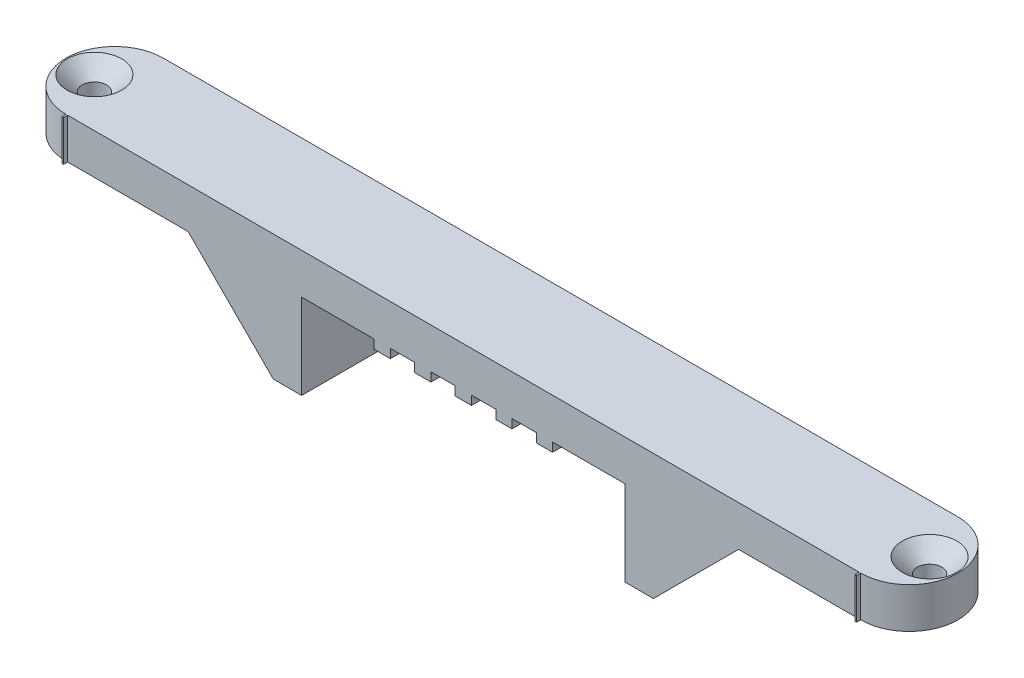
SolidWorks part; units mm, degrees
ref_plane "Front Plane" through (0, 0, 0) normal (0, 0, 1) x (1, 0, 0)
ref_plane "Top Plane" through (0, 0, 0) normal (0, 1, 0) x (1, 0, 0)
ref_plane "Right Plane" through (0, 0, 0) normal (1, 0, 0) x (0, 0, -1)
sketch "Sketch1" plane through (0, 0, 0) normal (0, 1, 0) x (1, 0, 0)
  line L0 (-49, 0) -> (49, 0) construction
  line L1 (-49, 6) -> (49, 6)
  line L2 (-49, -6) -> (49, -6)
  arc A0 (-49, 6) -> (-49, -6) centre (-49, 0) ccw
  arc A1 (49, -6) -> (49, 6) centre (49, 0) ccw
  circle A2 centre (-51.5, 0) radius 1.5
  circle A3 centre (51.5, 0) radius 1.5
  point P2 (0, 0)
  point P12 (-55, 0)
  point P13 (55, 0)
  dimension "D3" = 3
  dimension "D4" = 3.5
  dimension "D1" = 110
  dimension "D2" = 12
  dimension "D5" = 3.5
extrude "Boss-Extrude1" add sketch "Sketch1" along normal blind 3 contours L2 A1 L1 A0 | A2 | A3
sketch "Sketch4" plane through (0, 0, 0) normal (0, -1, 0) x (1, 0, 0)
  line L0 (-19.94, 6) -> (-19.94, -6)
  line L1 (-49, 6) -> (49, 6) construction
  line L2 (-49, -6) -> (49, -6) construction
  line L3 (-19.94, -6) -> (-23.44, -6)
  line L4 (-23.44, -6) -> (-23.44, 6)
  line L5 (-23.44, 6) -> (-19.94, 6)
  line L6 (0, 6) -> (0, -6) construction
  line L7 (-19.94, 5.075) -> (-19.94, -14.3256) construction
  line L8 (23.44, -6) -> (23.44, 6)
  line L9 (19.94, -6) -> (23.44, -6)
  line L10 (19.94, 6) -> (19.94, -6)
  line L11 (23.44, 6) -> (19.94, 6)
  dimension "D1" = 0
  dimension "D2" = 3.5
extrude "Boss-Extrude3" add sketch "Sketch4" along normal blind 10.5
sketch "Sketch5" plane through (0, 0, 0) normal (0, -1, 0) x (1, 0, 0)
  line L1 (4, 6) -> (4, -6)
  line L2 (4, 6) -> (6, 6)
  line L6 (-19.94, -6) -> (19.94, -6) construction
  line L7 (-1, 6) -> (1, 6)
  line L8 (-1, 6) -> (-1, -6)
  line L9 (-1, -6) -> (1, -6)
  line L10 (1, 6) -> (1, -6)
  line L11 (-1, 6) -> (1, -6) construction
  line L12 (-1, -6) -> (1, 6) construction
  line L13 (6, 6) -> (6, -6)
  line L14 (4, -6) -> (6, -6)
  line L15 (9, 6) -> (9, -6)
  line L16 (9, 6) -> (11, 6)
  line L17 (11, 6) -> (11, -6)
  line L18 (9, -6) -> (11, -6)
  line L19 (-4, 6) -> (-4, -6)
  line L20 (-6, -6) -> (-4, -6)
  line L21 (-6, 6) -> (-6, -6)
  line L22 (-6, 6) -> (-4, 6)
  line L23 (-9, 6) -> (-9, -6)
  line L24 (-11, -6) -> (-9, -6)
  line L25 (-11, 6) -> (-11, -6)
  line L26 (-11, 6) -> (-9, 6)
  point P0 (0, 0)
  dimension "D1" = 2
  dimension "D2" = 3
  dimension "D3" = 3
extrude "Boss-Extrude4" add sketch "Sketch5" along normal blind 1.1
sketch "Sketch6" plane through (0, 0, 6) normal (0, 0, 1) x (1, 0, 0)
  line L0 (49, 0) -> (49, 3)
  line L1 (49, 3) -> (48.8, 3)
  line L2 (-49, 3) -> (49, 3) construction
  line L3 (48.8, 3) -> (48.8, 0)
  line L4 (23.44, 0) -> (49, 0) construction
  line L5 (48.8, 0) -> (49, 0)
  line L6 (0, 0) -> (0, 3) construction
  line L7 (-48.8, 0) -> (-49, 0)
  line L8 (-48.8, 3) -> (-48.8, 0)
  line L9 (-49, 3) -> (-48.8, 3)
  line L10 (-49, 0) -> (-49, 3)
  dimension "D1" = 0.2
extrude "Boss-Extrude5" add sketch "Sketch6" along normal blind 0.5 contours L0 L1 L3 L5 | L8 L7 L10 L9
chamfer "Chamfer1" distance 10.5 2 edges at (23.44, 0, 0) (-23.44, 0, 0)
hole_wizard "Ø3.0mm Dowel Hole1" positions "Sketch7" profile "Sketch9" hole size "Ø3.0" standard "ANSI Metric" end condition up to next
sketch "Sketch7" plane through (0, 3, 0) normal (0, 1, 0) x (1, 0, 0)
  point P0 (-51.5, 0)
  point P2 (51.5, 0)
sketch "Sketch9" plane through (-51.5, 3, 0) normal (1, 0, 0) x (0, 0, 1)
  line L0 (0, 0) -> (0, 13.5)
  line L1 (0, 13.5) -> (1.5, 13.5)
  line L2 (1.5, 13.5) -> (1.5, 0)
  line L5 (1.5, 0) -> (0, 0)
  line L11 (0, -6.35) -> (0, 107.95) construction
  dimension "Thru Hole Dia." = 3
  dimension "Thru Hole Depth" = 13.5
sketch "Sketch10" plane through (0, 3, 0) normal (0, 1, 0) x (1, 0, 0)
  line L8 (-49, -6) -> (-49, -6.5)
  line L9 (-49, -6.5) -> (-48.8, -6.5)
  line L10 (-48.8, -6.5) -> (-48.8, -6)
  line L11 (-48.8, -6) -> (48.8, -6)
  line L12 (48.8, -6) -> (48.8, -6.5)
  line L13 (48.8, -6.5) -> (49, -6.5)
  line L14 (49, -6.5) -> (49, -6)
  line L15 (49, 6) -> (-49, 6)
  line L16 (-49, -6) -> (-49, -6.5)
  line L17 (-49, -6.5) -> (-48.8, -6.5)
  line L18 (-48.8, -6.5) -> (-48.8, -6)
  line L19 (-48.8, -6) -> (48.8, -6)
  line L20 (48.8, -6) -> (48.8, -6.5)
  line L21 (48.8, -6.5) -> (49, -6.5)
  line L22 (49, -6.5) -> (49, -6)
  line L23 (49, 6) -> (-49, 6)
  circle A0 centre (-51.5, 0) radius 1.5 construction
  circle A1 centre (-51.5, 0) radius 1.5
  arc A2 (-49, 6) -> (-49, -6) centre (-49, 0) ccw
  arc A3 (49, -6) -> (49, 6) centre (49, 0) ccw
  arc A4 (-49, 6) -> (-49, -6) centre (-49, 0) ccw
  arc A5 (49, -6) -> (49, 6) centre (49, 0) ccw
  circle A6 centre (51.5, 0) radius 1.5 construction
  circle A7 centre (51.5, 0) radius 1.5
  dimension "D1" = 0
extrude "Boss-Extrude6" add sketch "Sketch10" along normal blind 2 contours A4 L16 L17 L18 L19 L20 L21 L22 A5 L23
hole_wizard "CSK for M3 SFHCS1" positions "Sketch11" profile "Sketch12" countersink size "M3" standard "ANSI Metric"
sketch "Sketch11" plane through (0, 5, 0) normal (0, 1, 0) x (1, 0, 0)
  point P0 (51.5, 0)
  point P3 (-51.5, 0)
sketch "Sketch12" plane through (51.5, 5, 0) normal (1, 0, 0) x (0, 0, 1)
  line L0 (0, 0) -> (0, 32)
  line L1 (0, 32) -> (1.5, 31.0987)
  line L2 (1.5, 31.0987) -> (1.5, 1.86)
  line L3 (1.5, 1.86) -> (3.36, 0)
  line L5 (3.36, 0) -> (0, 0)
  line L6 (-1.5, 1.86) -> (-3.36, 0) construction
  line L10 (0, 32) -> (-1.5, 31.0987) construction
  line L11 (0, -6.35) -> (0, 107.95) construction
  dimension "Hole Dia." = 3
  dimension "Hole Depth" = 32
  dimension "Near C'Sink Dia." = 6.72
  dimension "Near C'Sink Angle" = 90
  dimension "Drill Angle" = 118
